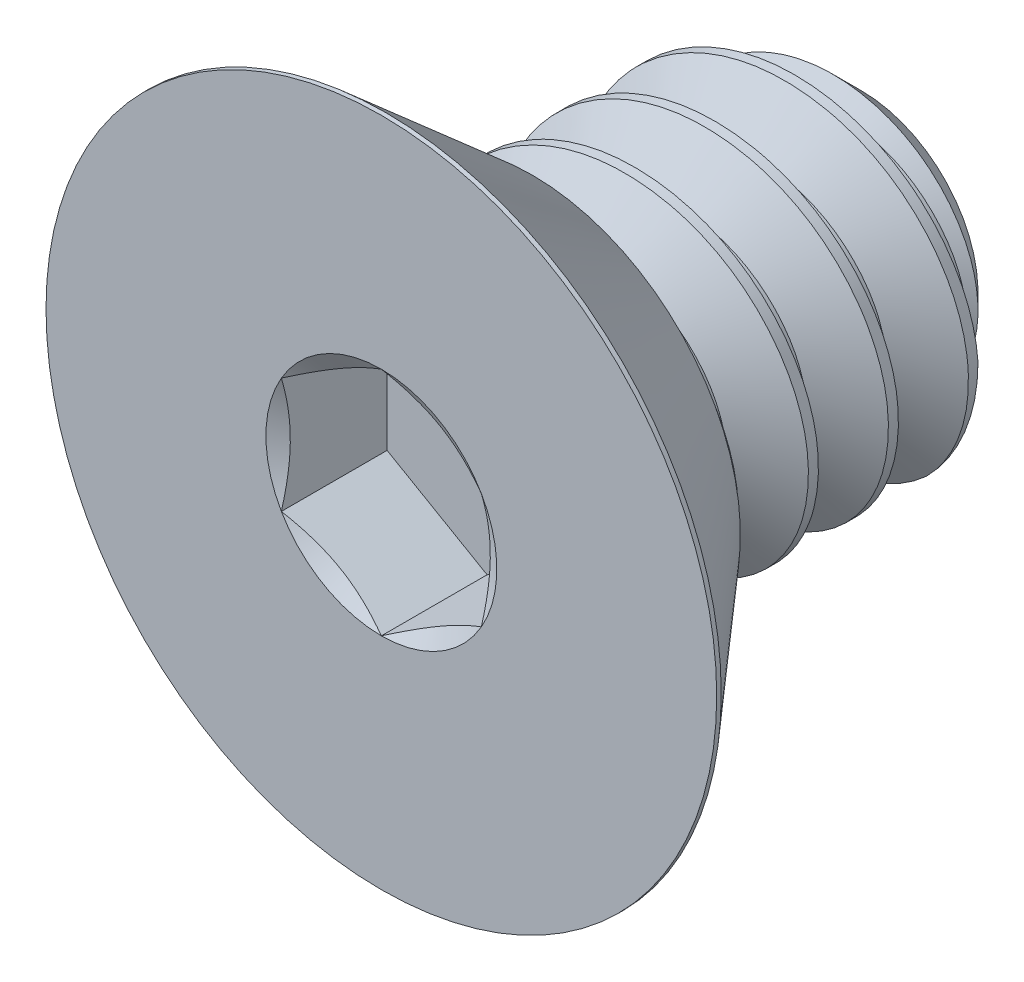
SolidWorks part; units mm, degrees
ref_plane "Front" through (0, 0, 0) normal (0, 0, 1) x (1, 0, 0)
ref_plane "Top" through (0, 0, 0) normal (0, 1, 0) x (1, 0, 0)
ref_plane "Right" through (0, 0, 0) normal (1, 0, 0) x (0, 0, -1)
sketch "Sketch1" plane through (0, 0, 0) normal (1, 0, 0) x (0, 0, -1)
  line L0 (0, 3.3274) -> (0.045, 3.3274) construction
  line L1 (0.045, 3.3274) -> (1.4986, 2.0638) construction
  line L2 (0, 1.7526) -> (4.7625, 1.7526)
  line L3 (4.7625, 1.7526) -> (4.7625, 0)
  line L4 (4.7625, 0) -> (0, 0)
  line L5 (0, 0) -> (0, 3.3274) construction
  line L6 (0, 3.3274) -> (0, -3.3274) construction
  line L7 (4.7625, 1.7526) -> (4.7625, -1.7526) construction
  line L8 (0, -3.3274) -> (0.045, -3.3274) construction
  line L9 (0.045, -3.3274) -> (1.4986, -2.0638) construction
  line L11 (0, 1.7526) -> (0, 0)
  line L12 (2.3309, 1.7526) -> (2.3309, 0) construction
  line L13 (-20.6375, 0) -> (-20.6375, 1.7526) construction
  arc A1 (1.4986, 2.0638) -> (2.3309, 1.7526) centre (2.3309, 3.0212) ccw construction
  dimension "D1" = 0.045
  dimension "Min Thread" = 25.4
revolve "Revolve1" add sketch "Sketch1" angle 360 mid plane about L4
sketch "Sketch3" plane through (0, 0, -4.7625) normal (0, 0, -1) x (-1, 0, 0)
  circle A0 centre (0, 0) radius 1.7526
curve "Helix/Spiral1" pitch 0.7937 height 4.7625 radius 1.7526 centre (0, 0, -4.7625) axis (0, 0, 1) start towards (0, 1, 0)
sketch "Sketch2" plane through (0, 0, 0) normal (1, 0, 0) x (0, 0, -1)
  line L0 (4.7625, 1.7526) -> (5.457, 1.7526)
  line L1 (5.457, 1.7526) -> (5.1594, 1.237)
  line L2 (5.1594, 1.237) -> (5.0602, 1.237)
  line L3 (5.0602, 1.237) -> (4.7625, 1.7526)
  line L4 (4.9113, 1.4948) -> (5.3082, 1.4948) construction
  dimension "D1" = 60
  dimension "D2" = 0.0992
  dimension "D3" = 0.3969
ref_plane "Plane2" through (0, 0, 20.6375) normal (0, 0, 1) x (1, 0, 0)
chamfer "Chamfer1" distance 0.5953 angle 45 1 edges at (0, 1.7526, -4.7625)
sweep "Cut-Sweep1" cut profiles "Sketch2" path "Helix/Spiral1" align with end faces yes
sketch "Sketch7" plane through (0, 0, 0) normal (1, 0, 0) x (0, 0, -1)
  line L0 (0, 3.3274) -> (0.045, 3.3274) construction
  line L1 (0.045, 3.3274) -> (1.4986, 2.0638) construction
  line L2 (0, 3.3274) -> (0.045, 3.3274)
  line L3 (0.045, 3.3274) -> (1.4986, 2.0638)
  line L6 (1.4986, 2.0638) -> (1.4986, 0)
  line L7 (0, 0) -> (0, 3.3274) construction
  line L8 (0, 0) -> (0, 3.3274)
  line L9 (0, 0) -> (1.4986, 0)
  line L10 (13.97, 0) -> (-13.97, 0) construction
revolve "Revolve2" add sketch "Sketch7" angle 360 mid plane about L9
ref_plane "Plane1" through (0, 0, -2.3309) normal (0, 0, 1) x (1, 0, 0)
sketch "Sketch8" plane through (0, 0, -1.4986) normal (0, 0, 1) x (1, 0, 0)
  circle A0 centre (0, 0) radius 1.7526
extrude "Boss-Extrude1" add sketch "Sketch8" against normal through all draft 46
sketch "Sketch5" plane through (0, 0, 0) normal (0, 0, 1) x (1, 0, 0)
  line L0 (0, 0) -> (-1.1457, 0) construction
  line L1 (0, 0) -> (-2.7496, 1.5875) construction
  line L2 (0, 0) -> (-2.7496, -1.5875) construction
  line L6 (0, 1.1457) -> (0, 0.9449) construction
  line L7 (0, 0.9449) -> (0, 0.7441) construction
  line L9 (0, 1.1457) -> (-0.9922, 0.5728)
  line L10 (-0.9922, 0.5728) -> (-0.9922, -0.5728)
  line L11 (-0.9922, -0.5728) -> (0, -1.1457)
  line L12 (0, -1.1457) -> (0.9922, -0.5728)
  line L13 (0.9922, -0.5728) -> (0.9922, 0.5728)
  line L14 (0.9922, 0.5728) -> (0, 1.1457)
  circle A0 centre (0, 0) radius 1.1457 construction
  circle A1 centre (0, 0) radius 0.9449 construction
  circle A2 centre (0, 0) radius 0.7441 construction
  circle A3 centre (0, 0) radius 0.9922 construction
  dimension "D3" = 1.4883
  dimension "D4" = 30
  dimension "D5" = 30
  dimension "Hex" = 1.9844
extrude "Cut-Extrude2" cut sketch "Sketch5" against normal blind 1.049
sketch "Sketch6" plane through (0, 0, 0) normal (0, 0, 1) x (1, 0, 0)
  circle A0 centre (0, 0) radius 1.1457
extrude "Cut-Extrude3" cut sketch "Sketch6" against normal blind 1.049 draft 60
sketch "Sketch9" [suppressed] plane through (0, 0, -2.3309) normal (0, 0, 1) x (1, 0, 0)
  circle A1 centre (0, 0) radius 1.7526
  circle A2 centre (0, 0) radius 1.7526
  point P0 (0, 1.7526)
  dimension "D1" = 0
extrude "Boss-Extrude2" [suppressed] add sketch "Sketch9" against normal up to surface (22.9684 mm away) up to plane "Plane2"
sketch "Sketch10" plane through (0, 0, 0) normal (1, 0, 0) x (0, 0, -1)
  line L0 (4.7625, 1.7526) -> (4.7625, -1.7526) construction
  point P0 (3.5719, -1.7526)
  dimension "D1" = 1.1906
equation "\"D3@Helix/Spiral1\" = \"Lg@Sketch1\""
equation "\"D2@Sketch2\" = \"D4@Helix/Spiral1\" * .125"
equation "\"D3@Sketch2\" = \"D4@Helix/Spiral1\" * .5"
equation "\"D1@Chamfer1\" = \"D4@Helix/Spiral1\" * .75"
equation "\"D1@Cut-Extrude2\" = \"Head Ht@Sketch1\" * .7"
equation "\"D1@Sketch1\" = \"Head Ht@Sketch1\" * .03"
equation "\"D1@Sketch10\" = \"D4@Helix/Spiral1\" * 1.5"
equation "\"D1@Cut-Extrude3\" = \"D1@Cut-Extrude2\""
equation "\"D3@Sketch5\" = \"Hex@Sketch5\" * .75"
